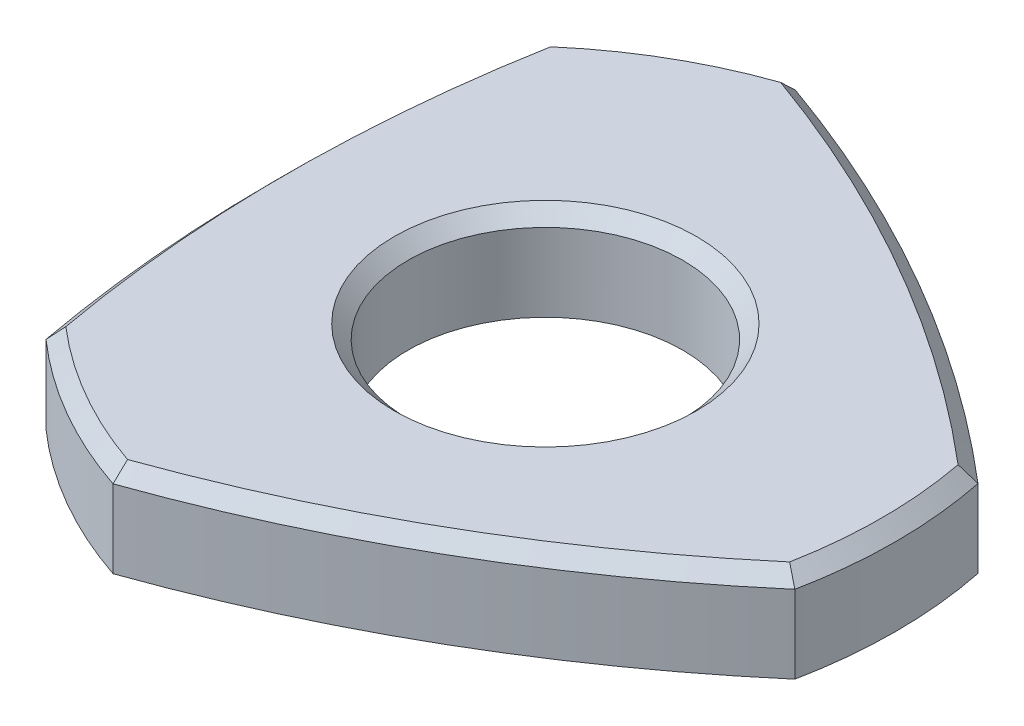
SolidWorks part; units mm, degrees
ref_plane "Front Plane" through (0, 0, 0) normal (0, 0, 1) x (1, 0, 0)
ref_plane "Top Plane" through (0, 0, 0) normal (0, 1, 0) x (1, 0, 0)
ref_plane "Right Plane" through (0, 0, 0) normal (1, 0, 0) x (0, 0, -1)
sketch "Sketch1" plane through (0, 0, 0) normal (0, 1, 0) x (1, 0, 0)
  line L0 (-54.5596, 54.5) -> (-19.9186, 74.5) construction
  line L1 (109.1192, 0) -> (-54.5596, 94.5) construction
  line L2 (-54.5596, 94.5) -> (-54.5596, -94.5) construction
  line L3 (-54.5596, -94.5) -> (109.1192, 0) construction
  line L4 (74.4782, 20) -> (74.4782, -20) construction
  line L5 (-19.9186, -74.5) -> (-54.5596, -54.5) construction
  line L6 (-59.5596, 0) -> (-54.5596, 0) construction
  line L7 (-38.2391, 66.2321) -> (-37.2391, 64.5) construction
  line L8 (29.7798, 51.5801) -> (27.2798, 47.25) construction
  line L9 (76.4782, 0) -> (74.4782, 0) construction
  line L10 (29.7798, -51.5801) -> (27.2798, -47.25) construction
  line L11 (-38.2391, -66.2321) -> (-37.2391, -64.5) construction
  line L18 (-54.5596, 94.5) -> (0, 0) construction
  line L19 (0, 0) -> (-54.5596, -94.5) construction
  line L20 (0, 0) -> (109.1192, 0) construction
  circle A0 centre (0, 0) radius 30
  arc A2 (-54.5596, 54.5) -> (-54.5596, -54.5) centre (239.9654, 0) ccw
  arc A3 (-19.9186, 74.5) -> (74.4782, 20) centre (-119.9827, -207.8161) cw
  arc A5 (74.4782, -20) -> (-19.9186, -74.5) centre (-119.9827, 207.8161) cw
  arc A7 (-54.5596, 54.5) -> (-19.9186, 74.5) centre (12.2609, -21.2365) cw
  arc A8 (-54.5596, -54.5) -> (-19.9186, -74.5) centre (12.2609, 21.2365) ccw
  arc A9 (74.4782, -20) -> (74.4782, 20) centre (-24.5218, 0) ccw
  spline S0 degree 1 poles (-54.5596, 54.5) (-19.9186, 74.5) knots 0 0 1 1 construction
  point P24 (0, 0)
  point P37 (0, 0)
  point P38 (81.8678, 0)
  point P39 (84.4372, 0)
  point P40 (74.4782, 0)
  dimension "D1" = 60
  dimension "D2" = 109
  dimension "D4" = 5
  dimension "D3" = 40
  dimension "D5" = 2
extrude "Boss-Extrude1" add sketch "Sketch1" along normal blind 20
chamfer "Chamfer1" distance 3 angle 45 7 edges at (0, 20, 30) (29.7798, 20, -51.5801) (76.4782, 20, 0) (29.7798, 20, 51.5801) (-38.2391, 20, 66.2321) (-59.5596, 20, 0) (-38.2391, 20, -66.2321)
